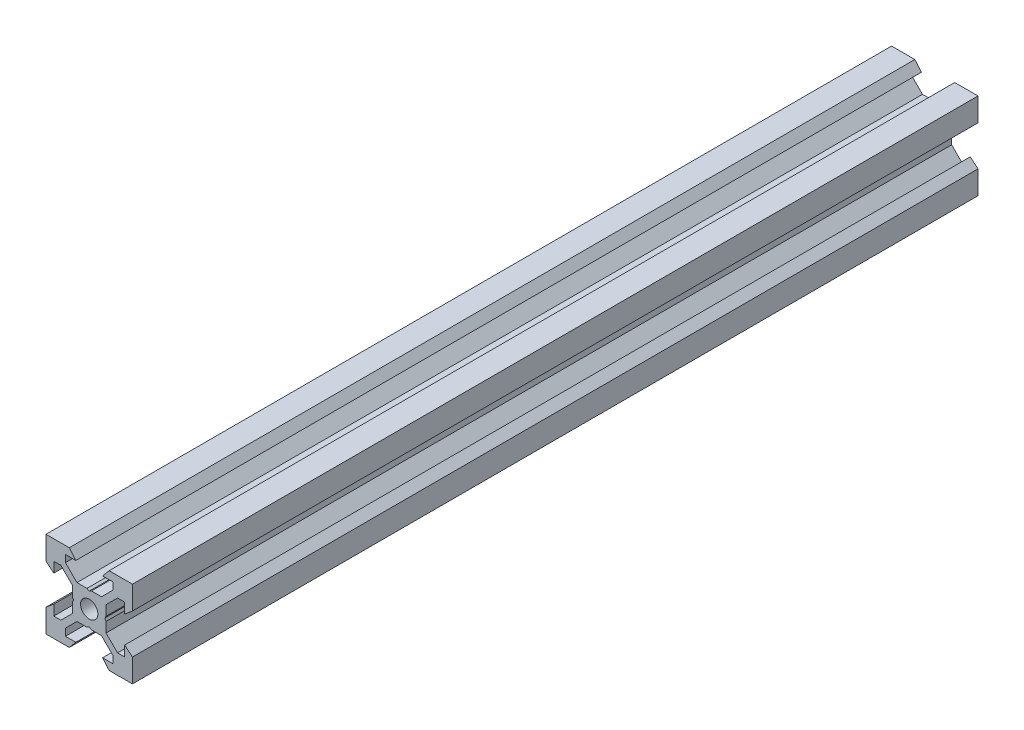
SolidWorks part; units mm, degrees
ref_plane "Front Plane" through (0, 0, 0) normal (0, 0, 1) x (1, 0, 0)
ref_plane "Top Plane" through (0, 0, 0) normal (0, 1, 0) x (1, 0, 0)
ref_plane "Right Plane" through (0, 0, 0) normal (1, 0, 0) x (0, 0, -1)
sketch "Sketch1" plane through (0, 0, 0) normal (0, 0, 1) x (1, 0, 0)
  line L0 (10, 10) -> (4.6104, 10) construction
  line L1 (10, 10) -> (10, 4.6104) construction
  line L2 (10, -10) -> (10, -4.6104) construction
  line L3 (10, -10) -> (4.6104, -10) construction
  line L4 (10, 10) -> (10, 4.6104)
  line L5 (6.5607, 5.5) -> (8.2, 5.5)
  line L6 (5.5, 8.2) -> (5.5, 6.5607)
  line L7 (10, 10) -> (4.6104, 10)
  line L8 (10, 10) -> (10, 4.6104)
  line L9 (6.5607, 5.5) -> (3.9, 2.8393)
  line L10 (5.5, 6.5607) -> (2.8393, 3.9)
  line L11 (10, 4.6104) -> (8.2, 3.1)
  line L12 (4.6104, 10) -> (3.1, 8.2)
  line L13 (8.2, 3.1) -> (8.2, 5.5)
  line L14 (3.1, 8.2) -> (5.5, 8.2)
  line L15 (-6.5607, 5.5) -> (-8.2, 5.5)
  line L16 (6.5607, -5.5) -> (8.2, -5.5)
  line L17 (3.1, -8.2) -> (5.5, -8.2)
  line L18 (8.2, -3.1) -> (8.2, -5.5)
  line L19 (4.6104, -10) -> (3.1, -8.2)
  line L20 (10, -4.6104) -> (8.2, -3.1)
  line L21 (0.5196, -3.9) -> (0, -3.6)
  line L22 (0.5196, 3.9) -> (0, 3.6)
  line L23 (3.6, 0) -> (3.9, -0.5196)
  line L24 (3.9, 0.5196) -> (3.6, 0)
  line L25 (3.9, 0.5196) -> (3.9, 2.8393)
  line L26 (2.8393, 3.9) -> (0.5196, 3.9)
  line L27 (3.9, -2.8393) -> (3.9, -0.5196)
  line L28 (2.8393, -3.9) -> (0.5196, -3.9)
  line L29 (5.5, -6.5607) -> (2.8393, -3.9)
  line L30 (6.5607, -5.5) -> (3.9, -2.8393)
  line L31 (10, -10) -> (10, -4.6104)
  line L32 (10, -10) -> (4.6104, -10)
  line L33 (5.5, -8.2) -> (5.5, -6.5607)
  line L34 (-6.5607, -5.5) -> (-8.2, -5.5)
  line L35 (10, -10) -> (10, -4.6104)
  line L36 (0, 0) -> (0, 8.2) construction
  line L37 (-10, -10) -> (-4.6104, -10) construction
  line L38 (-10, -10) -> (-10, -4.6104) construction
  line L39 (-10, 10) -> (-10, 4.6104) construction
  line L40 (-10, 10) -> (-4.6104, 10) construction
  line L41 (-10, -10) -> (-10, -4.6104)
  line L43 (-5.5, -8.2) -> (-5.5, -6.5607)
  line L44 (-10, -10) -> (-4.6104, -10)
  line L45 (-10, -10) -> (-10, -4.6104)
  line L46 (-6.5607, -5.5) -> (-3.9, -2.8393)
  line L47 (-5.5, -6.5607) -> (-2.8393, -3.9)
  line L48 (-2.8393, -3.9) -> (-0.5196, -3.9)
  line L49 (-3.9, -2.8393) -> (-3.9, -0.5196)
  line L50 (-2.8393, 3.9) -> (-0.5196, 3.9)
  line L51 (-3.9, 0.5196) -> (-3.9, 2.8393)
  line L52 (-3.9, 0.5196) -> (-3.6, 0)
  line L53 (-3.6, 0) -> (-3.9, -0.5196)
  line L54 (-0.5196, 3.9) -> (0, 3.6)
  line L55 (-0.5196, -3.9) -> (0, -3.6)
  line L56 (-10, -4.6104) -> (-8.2, -3.1)
  line L57 (-4.6104, -10) -> (-3.1, -8.2)
  line L58 (-8.2, -3.1) -> (-8.2, -5.5)
  line L59 (-3.1, -8.2) -> (-5.5, -8.2)
  line L60 (-10, -10) -> (10, -10) construction
  line L61 (-10, -10) -> (-10, 10) construction
  line L62 (-3.1, 8.2) -> (-5.5, 8.2)
  line L63 (-8.2, 3.1) -> (-8.2, 5.5)
  line L64 (-4.6104, 10) -> (-3.1, 8.2)
  line L65 (-10, 4.6104) -> (-8.2, 3.1)
  line L66 (-5.5, 6.5607) -> (-2.8393, 3.9)
  line L67 (-6.5607, 5.5) -> (-3.9, 2.8393)
  line L68 (-10, 10) -> (-10, 4.6104)
  line L69 (-10, 10) -> (-4.6104, 10)
  line L70 (-5.5, 8.2) -> (-5.5, 6.5607)
  line L71 (-10, 10) -> (10, 10) construction
  line L72 (-10, 10) -> (-10, 4.6104)
  line L73 (10, -10) -> (10, 10) construction
  line L74 (-10, -10) -> (10, 10) construction
  line L75 (-10, 10) -> (10, -10) construction
  circle A0 centre (0, 0) radius 2
  dimension "D7" = 4
  dimension "D1" = 20
  dimension "D2" = 5.3896
  dimension "D3" = 4.5
  dimension "D4" = 50
  dimension "D5" = 1.8
  dimension "D6" = 1.5104
  dimension "D8" = 5.5
  dimension "D9" = 120
  dimension "D10" = 0.3
  dimension "D11" = 2.3197
  dimension "D12" = 7.8
  dimension "D13" = 7.8
  dimension "D14" = 1.5
  dimension "D15" = 2.6607
extrude "Boss-Extrude1" add sketch "Sketch1" along normal mid plane 195.69 contours L70 L62 L64 L69 L68 L65 L63 L15 L67 L51 L52 L53 L49 L46 L34 L58 L56 L41 L44 L57 L59 L43 L47 L48 L55 L21 L28 L29 L33 L17 L19 L32 L31 L20 L18 L16 L30 L27 L23 L24 L25 L9 L5 L13 L11 L4 L7 L12 L14 L6 L10 region at (9.7172, 7.3052, 0)
